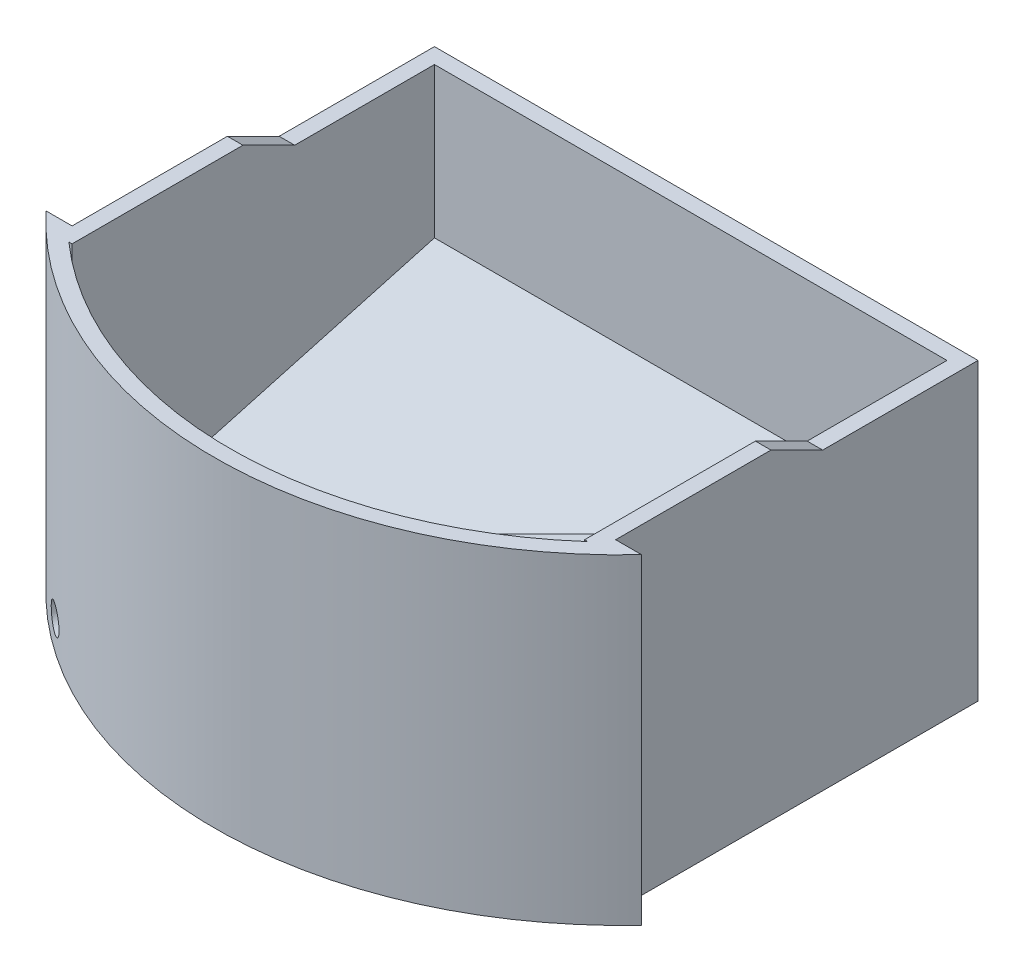
SolidWorks part; units mm, degrees
ref_plane "Front Plane" through (0, 0, 0) normal (0, 0, 1) x (1, 0, 0)
ref_plane "Top Plane" through (0, 0, 0) normal (0, 1, 0) x (1, 0, 0)
ref_plane "Right Plane" through (0, 0, 0) normal (1, 0, 0) x (0, 0, -1)
sketch "Sketch4" plane through (0, 0, 0) normal (0, 1, 0) x (1, 0, 0)
  line L0 (-6.35, 0) -> (139.7, 0)
  line L1 (0, 0) -> (133.35, 0)
  line L2 (0, 0) -> (0, 88.9)
  line L3 (0, 88.9) -> (133.35, 88.9)
  line L4 (133.35, 0) -> (133.35, 88.9)
  arc A1 (-6.35, 0) -> (139.7, 0) centre (66.675, 68.1037) ccw
  point P6 (66.675, -31.75)
  point P9 (66.675, 0)
  dimension "D1" = 133.35
  dimension "D2" = 88.9
  dimension "D3" = 146.05
  dimension "D4" = 6.35
  dimension "D5" = 31.75
extrude "Boss-Extrude2" add sketch "Sketch4" along normal blind 78.74 contours L0 A1 | L0 L4 L3 L2 region at (66.675, 0, 12.8907) region at (66.675, 0, -44.45)
sketch "Sketch5" plane through (0, 0, 0) normal (1, 0, 0) x (0, 0, -1)
  line L0 (0, 78.74) -> (88.9, 78.74) construction
  line L1 (0, 78.74) -> (88.9, 78.74)
  line L2 (88.9, 78.74) -> (88.9, 72.39)
  line L3 (88.9, 78.74) -> (88.9, 0) construction
  line L4 (88.9, 72.39) -> (50.8, 72.39)
  line L5 (50.8, 72.39) -> (38.1, 78.74)
  line L6 (38.1, 78.74) -> (88.9, 78.74)
  dimension "D1" = 12.7
  dimension "D2" = 38.1
  dimension "D3" = 6.35
extrude "Cut-Extrude4" cut sketch "Sketch5" along normal through all contours L2 L4 L5 L6
ref_plane "Plane1" through (3.81, 0, 0) normal (1, 0, 0) x (0, 0, -1)
ref_plane "Plane2" through (129.54, 0, 0) normal (1, 0, 0) x (0, 0, -1)
ref_plane "Plane3" through (0, 0, -85.09) normal (0, 0, -1) x (-1, 0, 0)
ref_plane "Plane4" through (0, 15.24, 0) normal (0, 1, 0) x (1, 0, 0)
ref_plane "Plane5" through (0, 0, 28.448) normal (0, 0, 1) x (1, 0, 0)
ref_plane "Plane6" through (15.24, 0, 0) normal (1, 0, 0) x (0, 0, -1)
ref_plane "Plane7" through (0, 0, -11.43) normal (0, 0, 1) x (1, 0, 0)
shell "Shell1" thickness 3.81 removed face at (66.675, 78.74, -7.4083) removed face at (66.675, 75.565, -44.45) removed face at (66.675, 72.39, -69.85)
sketch "Sketch8" plane through (0, 15.24, 0) normal (0, 1, 0) x (1, 0, 0)
  line L0 (0, 88.9) -> (133.35, 88.9) construction
  line L1 (133.35, 0) -> (133.35, 88.9) construction
  line L2 (-6.35, 0) -> (139.7, 0) construction
  line L3 (0, 0) -> (0, 88.9) construction
  line L4 (0, 88.9) -> (133.35, 88.9)
  line L5 (133.35, 0) -> (133.35, 88.9)
  line L6 (-6.35, 0) -> (139.7, 0)
  line L7 (0, 0) -> (0, 88.9)
  arc A0 (-6.35, 0) -> (139.7, 0) centre (66.675, 68.1037) ccw construction
  arc A1 (-6.35, 0) -> (139.7, 0) centre (66.675, 68.1037) ccw
extrude "fill in tube area" add sketch "Sketch8" against normal up to surface (15.24 mm away) contours L7 L6 L5 L4 | A1 L6 region at (66.675, 15.24, -44.45) up to plane "Top Plane"
sketch "Sketch7" plane through (3.81, 0, 0) normal (1, 0, 0) x (0, 0, -1)
  line L0 (-28.448, 78.74) -> (0, 15.24)
  line L1 (-28.448, 43.307) -> (-28.448, -43.307) construction
  line L2 (66.3575, 15.24) -> (-66.3575, 15.24) construction
  line L3 (0, 80.3275) -> (0, -80.3275) construction
  line L4 (0, 15.24) -> (-28.448, 15.24)
  line L5 (-28.448, 15.24) -> (-28.448, 78.74)
  line L6 (0, 78.74) -> (-31.75, 78.74) construction
  point P8 (0, 0)
extrude "Front inner slope" add sketch "Sketch7" along normal up to surface (125.73 mm away) up to plane "Plane2"
sketch "Sketch11" plane through (0, 15.24, 0) normal (0, 1, 0) x (1, 0, 0)
  line L0 (3.81, -43.307) -> (3.81, 43.307) construction
  line L1 (-6.35, 0) -> (139.7, 0) construction
  circle A0 centre (9.525, 5.715) radius 3.175
  dimension "D1" = 6.35
  dimension "D2" = 5.715
  dimension "D3" = 5.715
extrude "Cut-Extrude6" cut sketch "Sketch11" against normal blind 10.16
sketch "Sketch12" plane through (0, 0, -85.09) normal (0, 0, -1) x (-1, 0, 0)
  line L0 (-129.54, 35.56) -> (-15.24, 15.24)
  line L1 (-129.54, 43.307) -> (-129.54, -43.307) construction
  line L2 (-15.24, 43.307) -> (-15.24, -43.307) construction
  line L3 (66.3575, 15.24) -> (-66.3575, 15.24) construction
  line L4 (-15.24, 15.24) -> (-129.54, 15.24)
  line L5 (-129.54, 15.24) -> (-129.54, 35.56)
  dimension "D1" = 20.32
extrude "Inner Slope 1" add sketch "Sketch12" against normal up to surface (113.538 mm away) up to plane "Plane5"
sketch "Sketch9" plane through (0, 15.24, 0) normal (0, 1, 0) x (1, 0, 0)
  line L2 (-6.35, 0) -> (-6.35, -28.448)
  line L3 (-43.307, -28.448) -> (43.307, -28.448) construction
  line L4 (-6.35, -28.448) -> (41.2087, -28.448)
  line L5 (139.7, -28.448) -> (139.7, 0)
  line L6 (92.1413, -28.448) -> (139.7, -28.448)
  arc A0 (-6.35, 0) -> (139.7, 0) centre (66.675, 68.1037) ccw construction
  arc A1 (-6.35, 0) -> (41.2087, -28.448) centre (66.675, 68.1037) ccw
  arc A2 (92.1413, -28.448) -> (139.7, 0) centre (66.675, 68.1037) ccw
extrude "Remove extra inner slope material" cut sketch "Sketch9" along normal through all
sketch "Sketch13" plane through (3.81, 0, 0) normal (1, 0, 0) x (0, 0, -1)
  line L0 (85.09, 35.56) -> (11.43, 15.24)
  line L1 (85.09, -39.8145) -> (85.09, 39.8145) construction
  line L2 (11.43, 43.307) -> (11.43, -43.307) construction
  line L3 (66.3575, 15.24) -> (-66.3575, 15.24) construction
  line L4 (11.43, 15.24) -> (85.09, 15.24)
  line L5 (85.09, 15.24) -> (85.09, 35.56)
  dimension "D1" = 20.32
extrude "Inner Slope 2" add sketch "Sketch13" along normal up to surface (125.73 mm away) up to plane "Plane2"
sketch "Sketch14" plane through (0, 0, 0) normal (0, 0, 1) x (1, 0, 0)
  line L0 (0, -43.307) -> (0, 43.307) construction
  line L1 (66.3575, 15.24) -> (-66.3575, 15.24) construction
  circle A0 centre (9.525, 6.985) radius 3.175
  dimension "D3" = 6.35
  dimension "D1" = 9.525
  dimension "D2" = 8.255
extrude "Cut-Extrude7" cut sketch "Sketch14" against normal blind 8.89 and the other way through all
sketch "Sketch15" plane through (0, 0, 0) normal (0, 1, 0) x (1, 0, 0)
  line L0 (0, 88.9) -> (133.35, 88.9) construction
  line L1 (19.05, 88.9) -> (23.368, 88.9)
  line L2 (19.05, 88.9) -> (19.05, 12.7)
  line L3 (19.05, 12.7) -> (23.368, 12.7)
  line L4 (23.368, 88.9) -> (23.368, 12.7)
  line L5 (133.35, 0) -> (133.35, 88.9) construction
  line L6 (114.3, 88.9) -> (109.982, 88.9)
  line L7 (114.3, 88.9) -> (114.3, 12.7)
  line L8 (114.3, 12.7) -> (109.982, 12.7)
  line L9 (109.982, 88.9) -> (109.982, 12.7)
  line L10 (0, 0) -> (0, 88.9) construction
  line L11 (-6.35, 0) -> (139.7, 0) construction
  dimension "D1" = 4.318
  dimension "D2" = 4.318
  dimension "D3" = 19.05
  dimension "D4" = 19.05
  dimension "D5" = 12.7
extrude "Cut-Extrude8" cut sketch "Sketch15" along normal blind 3.556
